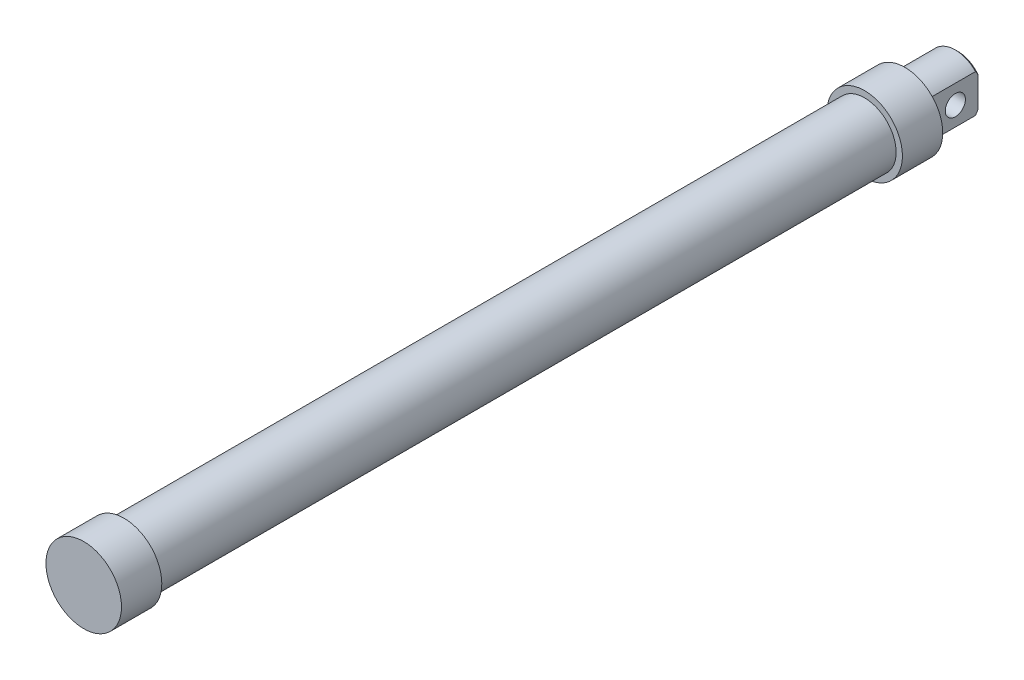
SolidWorks part; units mm, degrees
ref_plane "Plan de face" through (0, 0, 0) normal (0, 0, 1) x (1, 0, 0)
ref_plane "Plan de dessus" through (0, 0, 0) normal (0, 1, 0) x (1, 0, 0)
ref_plane "Plan de droite" through (0, 0, 0) normal (1, 0, 0) x (0, 0, -1)
sketch "Esquisse1" plane through (0, 0, 0) normal (0, 0, 1) x (1, 0, 0)
  circle A0 centre (0, 0) radius 12.5
  dimension "D1" = 25
extrude "Boss.-Extru.1" add sketch "Esquisse1" along normal blind 326
sketch "Esquisse2" plane through (0, 0, 326) normal (0, 0, 1) x (1, 0, 0)
  circle A0 centre (0, 0) radius 15
  dimension "D1" = 30
extrude "Boss.-Extru.2" add sketch "Esquisse2" against normal blind 16
extrude "Boss.-Extru.4" add sketch "Esquisse2<2>" along normal blind 16 from offset 326 offset against normal yes
sketch "Esquisse2<2>" plane through (0, 0, 326) normal (0, 0, 1) x (1, 0, 0) same geometry as "Esquisse2"
sketch "Esquisse3" plane through (0, 0, 0) normal (0, 0, -1) x (-1, 0, 0)
  circle A0 centre (0, 0) radius 11
  dimension "D1" = 22
extrude "Boss.-Extru.5" add sketch "Esquisse3" along normal blind 21
sketch "Esquisse4" plane through (0, 0, -21) normal (0, 0, -1) x (-1, 0, 0)
  line L0 (0, -11) -> (0, 11) construction
  line L1 (-8, -11) -> (0, -11) construction
  line L2 (-8, 11) -> (-13, 11)
  line L3 (-8, 11) -> (-8, -11)
  line L4 (-8, -11) -> (-13, -11)
  line L5 (-13, 11) -> (-13, -11)
  line L6 (-8, 11) -> (0, 11) construction
  line L7 (13, 11) -> (13, -11)
  line L8 (8, -11) -> (13, -11)
  line L9 (8, 11) -> (8, -11)
  line L10 (8, 11) -> (13, 11)
  circle A0 centre (0, 0) radius 11 construction
  circle A1 centre (0, 0) radius 11 construction
  dimension "D1" = 16
  dimension "D2" = 5
extrude "Enlèv. mat.-Extru.1" cut sketch "Esquisse4" against normal blind 19
chamfer "Chanfrein1" distance 1 angle 45 4 edges at (-8, 0, -2) (8, 0, -2) (0, -11, -21) (0, 11, -21)
sketch "Esquisse5" plane through (8, 0, 0) normal (1, 0, 0) x (0, 0, -1)
  line L0 (12, 0) -> (21, 0) construction
  line L1 (21, -6) -> (21, 6) construction
  line L2 (0, -15) -> (0, 15) construction
  circle A0 centre (12, 0) radius 4
  dimension "D2" = 8
  dimension "D1" = 12
extrude "Enlèv. mat.-Extru.2" cut sketch "Esquisse5" against normal through all
